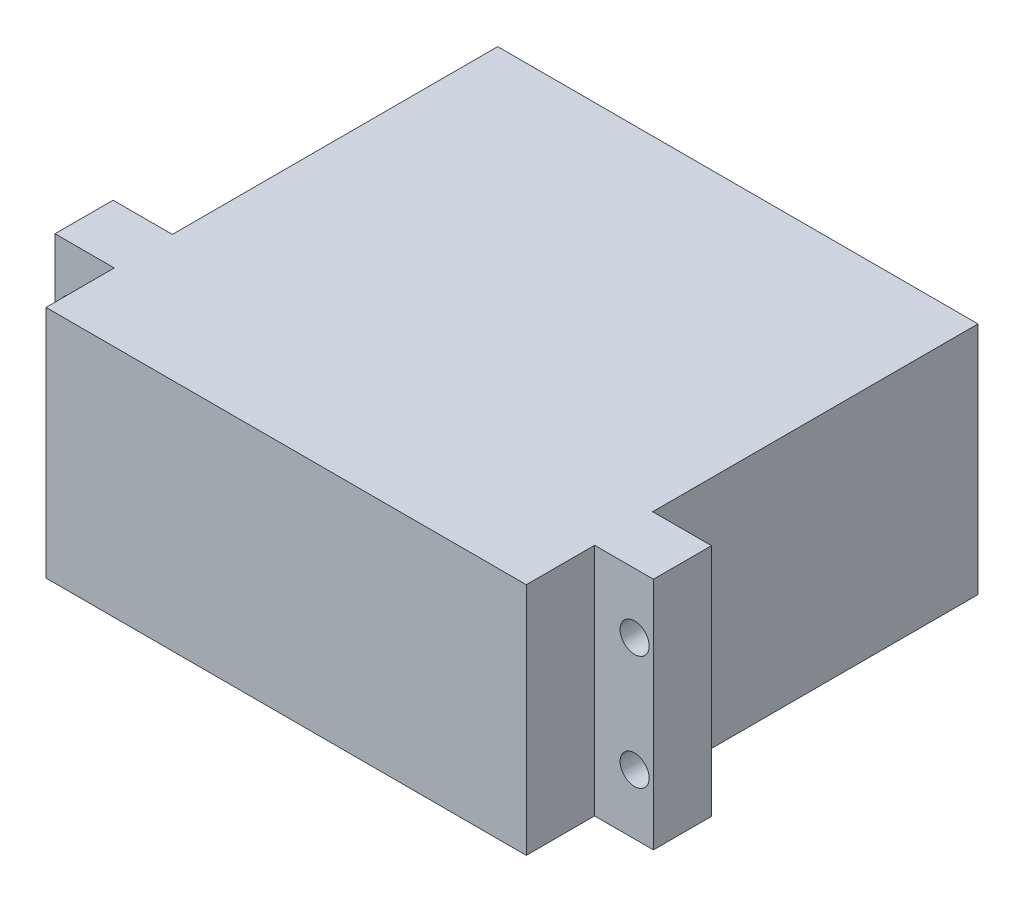
SolidWorks part; units mm, degrees
ref_plane "Front Plane" through (0, 0, 0) normal (0, 0, 1) x (1, 0, 0)
ref_plane "Top Plane" through (0, 0, 0) normal (0, 1, 0) x (1, 0, 0)
ref_plane "Right Plane" through (0, 0, 0) normal (1, 0, 0) x (0, 0, -1)
sketch "Sketch1" plane through (0, 0, 0) normal (0, 0, 1) x (1, 0, 0)
  line L1 (0, 0) -> (42, 0)
  line L2 (0, 0) -> (0, 20.5)
  line L3 (0, 20.5) -> (42, 20.5)
  line L4 (42, 0) -> (42, 20.5)
  dimension "D1" = 20.5
  dimension "D2" = 42
extrude "Boss-Extrude1" add sketch "Sketch1" along normal blind 39.5
ref_plane "Plane1" through (0, 0, 28.448) normal (0, 0, -1) x (-1, 0, 0)
sketch "Sketch2" plane through (0, 0, 28.448) normal (0, 0, -1) x (-1, 0, 0)
  line L0 (0, 0) -> (-42, 0) construction
  line L1 (-21, 20.5) -> (-21, 0) construction
  line L2 (0, 10.25) -> (-42, 10.25) construction
  line L3 (5.1851, 20.5) -> (-47.1446, 20.5)
  line L4 (5.1851, 20.5) -> (5.1851, 0)
  line L5 (-42, 20.5) -> (0, 20.5) construction
  line L6 (-42, 0) -> (-42, 20.5) construction
  line L7 (0, 20.5) -> (0, 0) construction
  line L8 (0, 0) -> (-42, 0)
  line L9 (-42, 20.5) -> (0, 20.5)
  line L10 (-42, 0) -> (-42, 20.5)
  line L11 (0, 20.5) -> (0, 0)
  line L12 (5.1851, 0) -> (-47.1446, 0)
  line L13 (-47.1446, 20.5) -> (-47.1446, 0)
  line L18 (-42, 20.5) -> (0, 20.5) construction
  line L19 (0, 0) -> (-42, 0) construction
  circle A0 centre (-45.5, 15.25) radius 1.27
  circle A1 centre (-45.5, 5.25) radius 1.27
  circle A2 centre (3.5, 15.25) radius 1.27
  circle A3 centre (3.5, 5.25) radius 1.27
  dimension "D5" = 2.54
  dimension "D1" = 49
  dimension "D2" = 10
  dimension "D3" = 49
  dimension "D4" = 10
extrude "Boss-Extrude2" add sketch "Sketch2" against normal blind 5.08 contours A3 A2 L3 L11 L12 | A1 L12 L10 L3 A0 region at (-2.4969, 10.25, 28.448) region at (44.4737, 10.25, 28.448)
